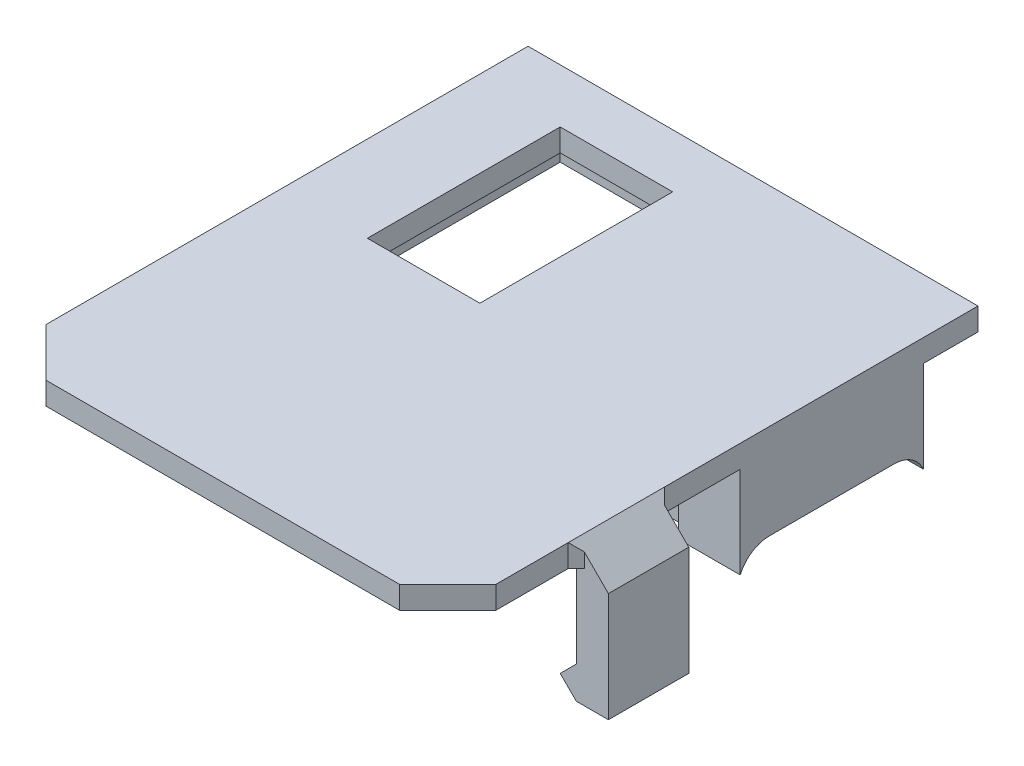
SolidWorks part; units mm, degrees
ref_plane "Płaszczyzna przednia" through (0, 0, 0) normal (0, 0, 1) x (1, 0, 0)
ref_plane "Płaszczyzna górna" through (0, 0, 0) normal (0, 1, 0) x (1, 0, 0)
ref_plane "Płaszczyzna prawa" through (0, 0, 0) normal (1, 0, 0) x (0, 0, -1)
sketch "Szkic1" plane through (0, 0, 0) normal (0, 1, 0) x (1, 0, 0)
  line L1 (-14, -16.5) -> (14, -16.5)
  line L2 (-14, -16.5) -> (-14, 16.5)
  line L3 (-14, 16.5) -> (14, 16.5)
  line L4 (14, -16.5) -> (14, 16.5)
  line L5 (-14, -16.5) -> (14, 16.5) construction
  line L6 (-14, 16.5) -> (14, -16.5) construction
  point P0 (0, 0)
  dimension "D1" = 28
  dimension "D2" = 33
extrude "Dodanie-wyciągnięcie1" add sketch "Szkic1" along normal blind 1.4
sketch "Szkic2" plane through (0, 0, 0) normal (0, -1, 0) x (1, 0, 0)
  line L5 (-9.15, 13.65) -> (-7.15, 13.65) construction
  line L6 (-10.15, -14.65) -> (10.15, -14.65)
  line L10 (-10.15, -14.65) -> (-10.15, 14.65)
  line L11 (-10.15, 14.65) -> (-9.15, 14.65)
  line L12 (10.15, -14.65) -> (10.15, 14.65)
  line L13 (-10.15, -14.65) -> (10.15, 14.65) construction
  line L14 (-10.15, 14.65) -> (10.15, -14.65) construction
  line L15 (9.15, 13.65) -> (9.15, -13.65)
  line L16 (9.15, -13.65) -> (-9.15, -13.65)
  line L17 (-9.15, -13.65) -> (-9.15, 13.65)
  line L18 (-14, 16.5) -> (14, 16.5) construction
  line L19 (-7.15, 14.65) -> (-7.15, 13.65) construction
  line L20 (14, 16.5) -> (14, -16.5) construction
  line L21 (7.15, 14.65) -> (7.15, 13.65) construction
  line L22 (-7.15, 13.65) -> (7.15, 13.65) construction
  line L23 (7.15, 13.65) -> (9.15, 13.65) construction
  line L24 (-7.15, 14.65) -> (7.15, 14.65) construction
  line L25 (9.15, 14.65) -> (10.15, 14.65)
  line L26 (-9.15, 13.65) -> (-9.15, 14.65)
  line L27 (9.15, 13.65) -> (9.15, 14.65)
  line L28 (-9.15, 14.65) -> (-7.15, 14.65) construction
  line L29 (7.15, 14.65) -> (9.15, 14.65) construction
  point P0 (0, 0)
  dimension "D1" = 3
  dimension "D2" = 1.85
  dimension "D3" = 1
  dimension "D4" = 1
  dimension "D5" = 1
  dimension "D6" = 1
  dimension "D7" = 3.85
  dimension "D8" = 3
extrude "Dodanie-wyciągnięcie2" add sketch "Szkic2" along normal blind 1
sketch "Szkic3" plane through (0, 0, 0) normal (0, -1, 0) x (1, 0, 0)
  line L0 (-9.15, -13.65) -> (-5.15, -13.65) construction
  line L1 (-5.15, -13.65) -> (-5.15, -7.15) construction
  line L2 (-9.15, -13.65) -> (9.15, -13.65) construction
  line L3 (-1.65, -13.15) -> (-8.65, -13.15)
  line L4 (-1.65, -13.15) -> (-1.65, -1.15)
  line L5 (-1.65, -1.15) -> (-8.65, -1.15)
  line L6 (-8.65, -13.15) -> (-8.65, -1.15)
  line L7 (-1.65, -13.15) -> (-8.65, -1.15) construction
  line L8 (-1.65, -1.15) -> (-8.65, -13.15) construction
  line L9 (-9.15, 14.65) -> (-9.15, -13.65) construction
  dimension "D1" = 4
  dimension "D2" = 6.5
  dimension "D3" = 12
  dimension "D4" = 7
extrude "Wytnij-wyciągnięcie1" cut sketch "Szkic3" against normal through all
sketch "Szkic4" plane through (10.15, 0, 0) normal (1, 0, 0) x (0, 0, -1)
  line L0 (16.5, 0) -> (13.1, 0) construction
  line L1 (16.5, 1.4) -> (16.5, 0) construction
  line L2 (-16.5, 0) -> (16.5, 0) construction
  line L3 (13.1, 0) -> (13.1, -5.6941)
  line L4 (13.1, 0) -> (1.7, 0)
  line L5 (1.7, 0) -> (1.7, -5.6941)
  line L6 (7.4, 0) -> (7.4, -4.5) construction
  line L7 (3.5305, -4.5) -> (11.2695, -4.5)
  line L8 (11.2695, -4.5) -> (11.2695, -6.5) construction
  arc A0 (11.2695, -4.5) -> (13.1, -5.6941) centre (11.2695, -6.5) cw
  arc A1 (3.5305, -4.5) -> (1.7, -5.6941) centre (3.5305, -6.5) ccw
  point P14 (7.4, -4.5)
  dimension "D1" = 3.4
  dimension "D2" = 11.4
  dimension "D3" = 4.5
  dimension "D5" = 2
extrude "Dodanie-wyciągnięcie3" add sketch "Szkic4" along normal up to surface (3.85 mm away) up to face at (14, 0.7, 0)
sketch "Szkic5" plane through (14, 0, 0) normal (1, 0, 0) x (0, 0, -1)
  line L0 (-16.5, 1.4) -> (-8.5, 1.4) construction
  line L1 (-16.5, 1.4) -> (16.5, 1.4) construction
  line L2 (-8.5, 1.4) -> (-8.5, -7.4)
  line L3 (-8.5, -7.4) -> (-3.5, -7.4)
  line L4 (-3.5, -7.4) -> (-3.5, 1.4)
  line L5 (-3.5, 1.4) -> (-8.5, 1.4)
  dimension "D1" = 8
  dimension "D2" = 8.8
  dimension "D3" = 5
extrude "Dodanie-wyciągnięcie4" add sketch "Szkic5" along normal blind 2
sketch "Szkic6" plane through (14, 0, 0) normal (-1, 0, 0) x (0, 0, 1)
  line L0 (8.5, 0) -> (8.5, -7.4) construction
  line L1 (3.5, -7.4) -> (8.5, -7.4)
  line L2 (3.5, -7.4) -> (3.5, -5.4)
  line L3 (3.5, -5.4) -> (8.5, -5.4)
  line L4 (8.5, -7.4) -> (8.5, -5.4)
  line L5 (3.5, -7.4) -> (8.5, -5.4) construction
  line L6 (3.5, -5.4) -> (8.5, -7.4) construction
  point P4 (6, -6.4)
  dimension "D1" = 2
extrude "Dodanie-wyciągnięcie5" add sketch "Szkic6" along normal blind 1
mirror "Lustro1" about plane through (0, 0, 0) normal (1, 0, 0) of "Dodanie-wyciągnięcie5", "Dodanie-wyciągnięcie4"
sketch "Szkic7" plane through (0, 0, -16.5) normal (0, 0, -1) x (-1, 0, 0)
  line L0 (-3, 1.4) -> (3, 1.4)
  line L1 (-14, 1.4) -> (14, 1.4) construction
  line L2 (3, 1.4) -> (3, -7.4)
  line L3 (3, -7.4) -> (-3, -7.4)
  line L4 (-3, -7.4) -> (-3, 1.4)
  point P5 (0, 1.4)
  dimension "D1" = 6
  dimension "D2" = 8.8
extrude "Dodanie-wyciągnięcie6" add sketch "Szkic7" along normal blind 2
sketch "Szkic8" plane through (0, 0, -16.5) normal (0, 0, 1) x (1, 0, 0)
  line L0 (3, 0) -> (3, -7.4) construction
  line L1 (-3, -7.4) -> (3, -7.4)
  line L2 (-3, -7.4) -> (-3, -5.4)
  line L3 (-3, -5.4) -> (3, -5.4)
  line L4 (3, -7.4) -> (3, -5.4)
  line L5 (-3, -7.4) -> (3, -5.4) construction
  line L6 (-3, -5.4) -> (3, -7.4) construction
  point P4 (0, -6.4)
  dimension "D1" = 2
extrude "Dodanie-wyciągnięcie7" add sketch "Szkic8" along normal blind 1
chamfer "Sfazowanie1" distance 1 angle 45 6 edges at (13, -7.4, 6) (13, -5.4, 6) (0, -7.4, -15.5) (0, -5.4, -15.5) (-13, -5.4, 6) (-13, -7.4, 6)
chamfer "Sfazowanie2" distance 2 angle 45 3 edges at (16, 1.4, 6) (0, 1.4, -18.5) (-16, 1.4, 6)
chamfer "Sfazowanie3" distance 0.5 angle 45 6 edges at (14, 0.7, 3.5) (-14, 0.7, 8.5) (-14, 0.7, 3.5) (-3, 0.7, -16.5) (3, 0.7, -16.5) (14, 0.7, 8.5)
sketch "Szkic9" plane through (0, 0, 0) normal (0, -1, 0) x (1, 0, 0)
  line L0 (-14, 16.5) -> (14, 16.5) construction
  line L2 (-7, 11.5) -> (7, 11.5)
  line L3 (-7, 11.5) -> (-7, 2.5)
  line L4 (-7, 2.5) -> (7, 2.5)
  line L5 (7, 11.5) -> (7, 2.5)
  line L6 (-7, 11.5) -> (7, 2.5) construction
  line L7 (-7, 2.5) -> (7, 11.5) construction
  dimension "D1" = 5
  dimension "D2" = 9
  dimension "D3" = 14
extrude "Dodanie-wyciągnięcie8" add sketch "Szkic9" along normal blind 2
chamfer "Sfazowanie4" distance 3 angle 45 2 edges at (14, 0.7, 16.5) (-14, 0.7, 16.5)
sketch "Szkic10" plane through (0, 0, 0) normal (0, -1, 0) x (1, 0, 0)
  line L0 (10.15, -13.1) -> (10.15, -1.7) construction
  line L1 (10.15, -3.5305) -> (5.15, -3.5305)
  line L2 (10.15, -3.5305) -> (10.15, -11.2695)
  line L3 (10.15, -11.2695) -> (5.15, -11.2695)
  line L4 (5.15, -3.5305) -> (5.15, -11.2695)
  line L5 (10.15, -3.5305) -> (5.15, -11.2695) construction
  line L6 (10.15, -11.2695) -> (5.15, -3.5305) construction
  line L7 (10.15, -3.5305) -> (10.15, -11.2695) construction
  point P4 (7.65, -7.4)
  dimension "D1" = 5
extrude "Dodanie-wyciągnięcie9" add sketch "Szkic10" along normal blind 6.6
